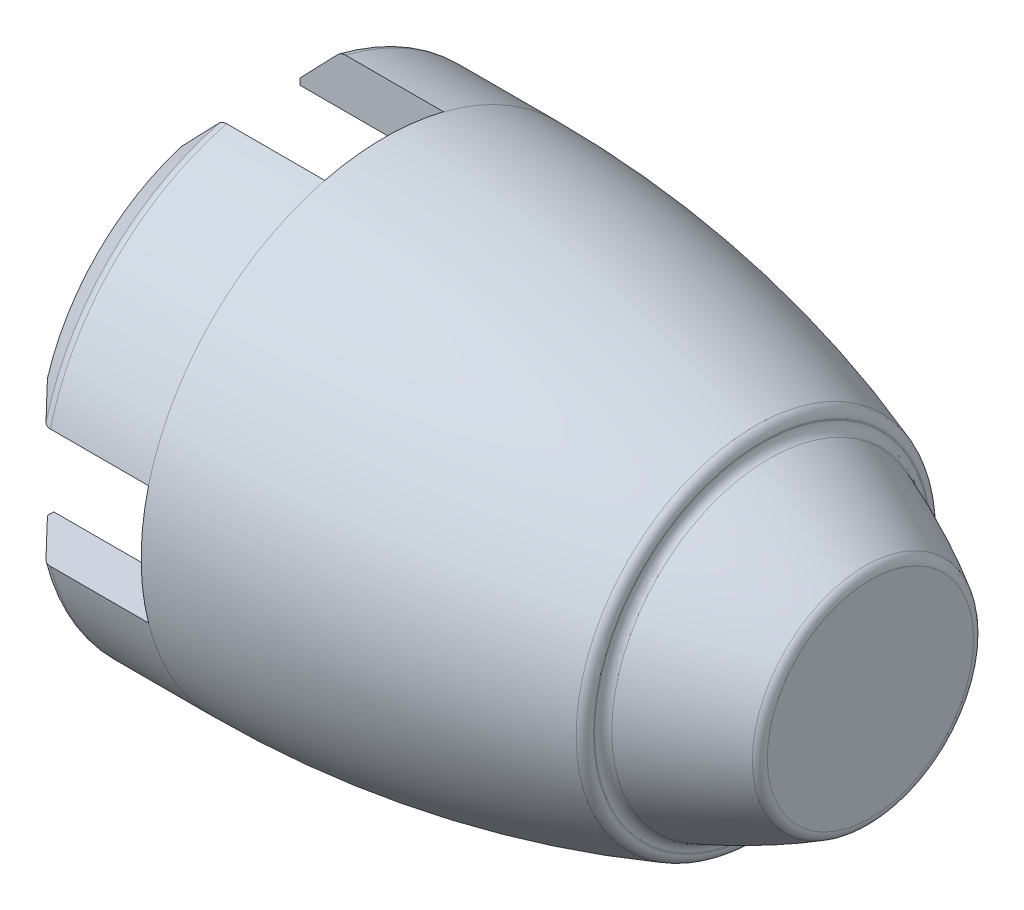
SolidWorks part; units mm, degrees
ref_plane "Front Plane" through (0, 0, 0) normal (0, 0, 1) x (1, 0, 0)
ref_plane "Top Plane" through (0, 0, 0) normal (0, 1, 0) x (1, 0, 0)
ref_plane "Right Plane" through (0, 0, 0) normal (1, 0, 0) x (0, 0, -1)
sketch "Sketch1" plane through (0, 0, 0) normal (0, 0, 1) x (1, 0, 0)
  line L0 (0, 9.2202) -> (0, 11.43)
  line L1 (0, 11.43) -> (7.62, 11.43)
  line L2 (25.4, 8.2949) -> (25.4, 7.5329)
  line L3 (20.2504, 10.1692) -> (47004.8815, -17090.838) construction
  line L4 (29.13, 6.1753) -> (47013.761, -17094.8319) construction
  line L7 (24.13, 6.858) -> (24.13, 0)
  line L8 (24.13, 0) -> (30.48, 0)
  line L9 (30.48, 0) -> (30.48, 5.1435)
  line L10 (24.13, 6.858) -> (9.398, 6.858)
  line L11 (9.398, 6.858) -> (9.398, 9.2202)
  line L12 (9.398, 9.2202) -> (0, 9.2202)
  arc A0 (7.62, 11.43) -> (25.4, 8.2949) centre (7.62, -40.5552) cw
  arc A1 (25.4, 7.5329) -> (30.48, 5.1435) centre (14.7875, -21.6246) cw
  dimension "D1" = 11.43
  dimension "D2" = 7.62
  dimension "D3" = 9.2202
  dimension "D4" = 20
  dimension "D5" = 25.4
  dimension "D6" = 5.1435
  dimension "D7" = 0.762
  dimension "D8" = 30.48
  dimension "D9" = 9.398
  dimension "D10" = 6.858
  dimension "D11" = 16.51
revolve "Revolve1" add sketch "Sketch1" angle 360 about L8
fillet "Fillet1" radius 0.508 3 edges at (25.4, 0, 8.2949) (25.4, 0, 7.5329) (30.48, 0, 5.1435)
sketch "Sketch2" plane through (0, 0, 0) normal (-1, 0, 0) x (0, 0, 1)
  line L1 (0, 2.794) -> (11.43, 2.794)
  line L2 (0, 2.794) -> (0, -2.794)
  line L3 (0, -2.794) -> (11.43, -2.794)
  line L4 (11.43, 2.794) -> (11.43, -2.794)
  circle A0 centre (0, 0) radius 11.43 construction
  point P4 (0, 0)
  dimension "D1" = 5.588
ref_plane "Plane1" through (7.62, 0, 0) normal (1, 0, 0) x (0, 0, -1)
chamfer "Chamfer1" distance 2.794 angle 45 1 edges at (0, 0, 11.43)
fillet "Fillet2" radius 0.508 1 edges at (2.794, 0, -11.43)
extrude "Cut-Extrude1" cut sketch "Sketch2" against normal up to surface (7.62 mm away) and the other way through all up to plane "Plane1"
pattern_circular "CirPattern1" count 4 over 360 about axis through (2.6452, 0, 0) along (-1, 0, 0) of "Cut-Extrude1"
sketch "Sketch3" plane through (24.13, 0, 0) normal (-1, 0, 0) x (0, 0, 1)
  circle A0 centre (7.62, 0) radius 1.016
  circle A3 centre (0, 0) radius 6.858 construction
  dimension "D1" = 2.032
  dimension "D2" = 0.254
extrude "Cut-Extrude3" cut sketch "Sketch3" along normal through all
fillet "Fillet3" radius 2.54 2 edges at (16.764, 0.6368, 6.8284) (16.764, -0.6368, 6.8284)
chamfer "Chamfer3" distance 0.4 angle 45 4 edges at (0.5842, -6.5197, -6.5197) (0.5842, 6.5197, -6.5197) (0.5842, -6.5197, 6.5197) (0.5842, 6.5197, 6.5197) first distance on face at (1.6147, -6.5193, -7.0551) first distance on face at (1.6147, 7.0551, -6.5193) first distance on face at (1.6147, -7.0551, 6.5193) first distance on face at (1.6147, 6.5193, 7.0551)
